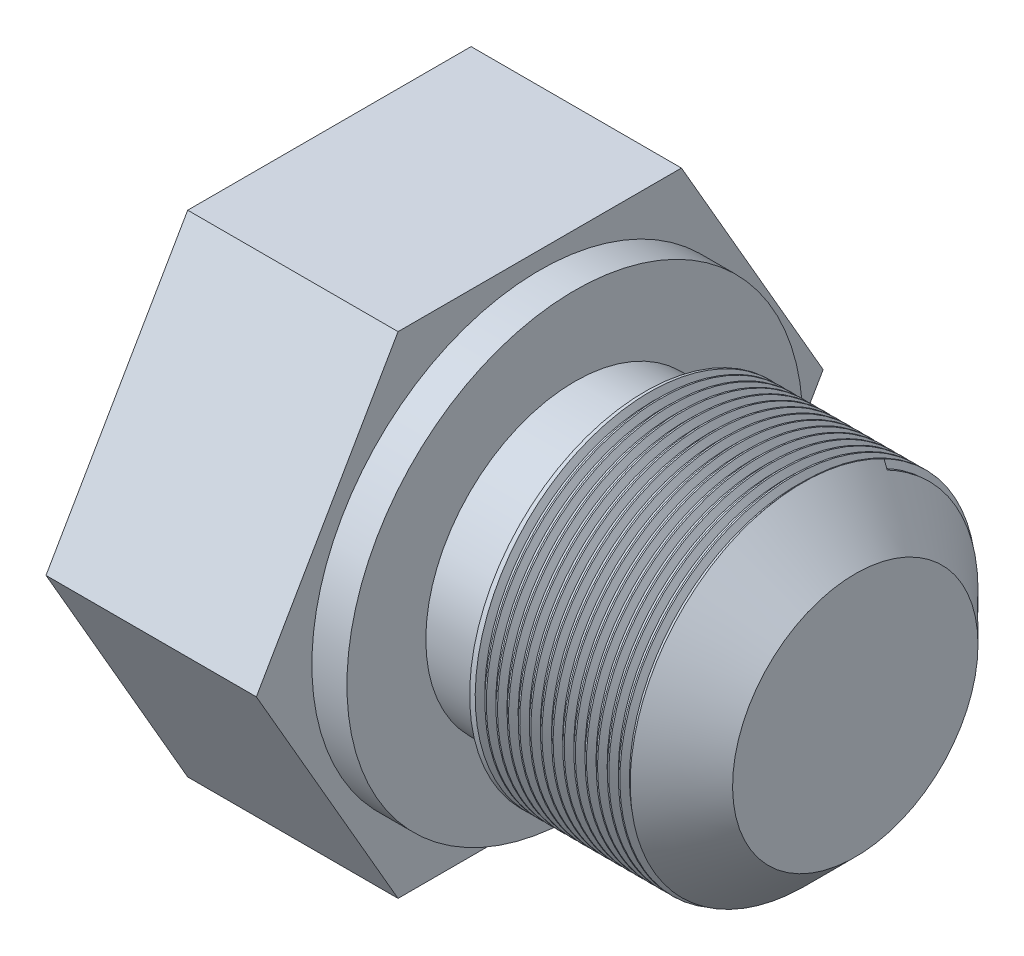
SolidWorks part; units mm, degrees
ref_plane "前视基准面" through (0, 0, 0) normal (0, 0, 1) x (1, 0, 0)
ref_plane "上视基准面" through (0, 0, 0) normal (0, 1, 0) x (1, 0, 0)
ref_plane "右视基准面" through (0, 0, 0) normal (1, 0, 0) x (0, 0, -1)
ref_axis "基准轴1" through (88.99, 0, 0) along (-1, 0, 0)
sketch "草图1" plane through (0, 0, 0) normal (1, 0, 0) x (0, 0, -1)
  circle A0 centre (0, 0) radius 6.5
extrude "凸台-拉伸1" add sketch "草图1" along normal blind 1
sketch "草图2" plane through (1, 0, 0) normal (1, 0, 0) x (0, 0, -1)
  circle A0 centre (0, 0) radius 4.25
extrude "凸台-拉伸2" add sketch "草图2" along normal blind 2
sketch "草图3" plane through (3, 0, 0) normal (1, 0, 0) x (0, 0, -1)
  circle A0 centre (0, 0) radius 5
extrude "凸台-拉伸3" add sketch "草图3" along normal blind 6
cosmetic thread "装饰螺纹线3" parameters "D2"=8.376
cosmetic thread "装饰螺纹线4" parameters "D1"=5, "D2"=8.376
chamfer "倒角1" distance 1.5 angle 45 1 edges at (9, 0, -5)
cosmetic thread "装饰螺纹线1" parameters "D2"=8.376
cosmetic thread "装饰螺纹线2" parameters "D1"=5, "D2"=8.376
sketch "草图4" plane through (0, 0, 0) normal (-1, 0, 0) x (0, 0, 1)
  line L1 (4.0415, -7) -> (8.0829, 0)
  line L2 (8.0829, 0) -> (4.0415, 7)
  line L3 (4.0415, 7) -> (-4.0415, 7)
  line L4 (-4.0415, 7) -> (-8.0829, 0)
  line L5 (-8.0829, 0) -> (-4.0415, -7)
  line L6 (-4.0415, -7) -> (4.0415, -7)
  circle A0 centre (0, 0) radius 7 construction
  dimension "D1" = 14
extrude "凸台-拉伸4" add sketch "草图4" along normal blind 6
thread "螺纹线1" pitch 0.3175 method cut profile "螺纹线轮廓1" start angle 0, offset 0, length 4.5, pitch 0.3175, diameter 10
ref_plane "基准面1" through (3, 0, -5) normal (0, -1, 0) x (0, 0, -1)
sketch "螺纹线轮廓1" plane through (3, 0, -5) normal (0, -1, 0) x (0, 0, -1)
  line L0 (0, 0) -> (0, 0.3175) construction
  line L11 (0, 0) -> (0, 0.2778)
  line L12 (0, 0.2778) -> (-0.1719, 0.1786)
  line L13 (-0.1719, 0.1786) -> (-0.1719, 0.0992)
  line L15 (-0.1719, 0.0992) -> (0, 0)
  line L17 (-0.1719, 0.1389) -> (0, 0.1389) construction
  point P2 (0, 0)
  dimension "Pitch" = 0.3175
  dimension "Profile_Angle" = 60
  dimension "Profile_Land" = 0.0794
  dimension "Profile_Height" = 0.1719
